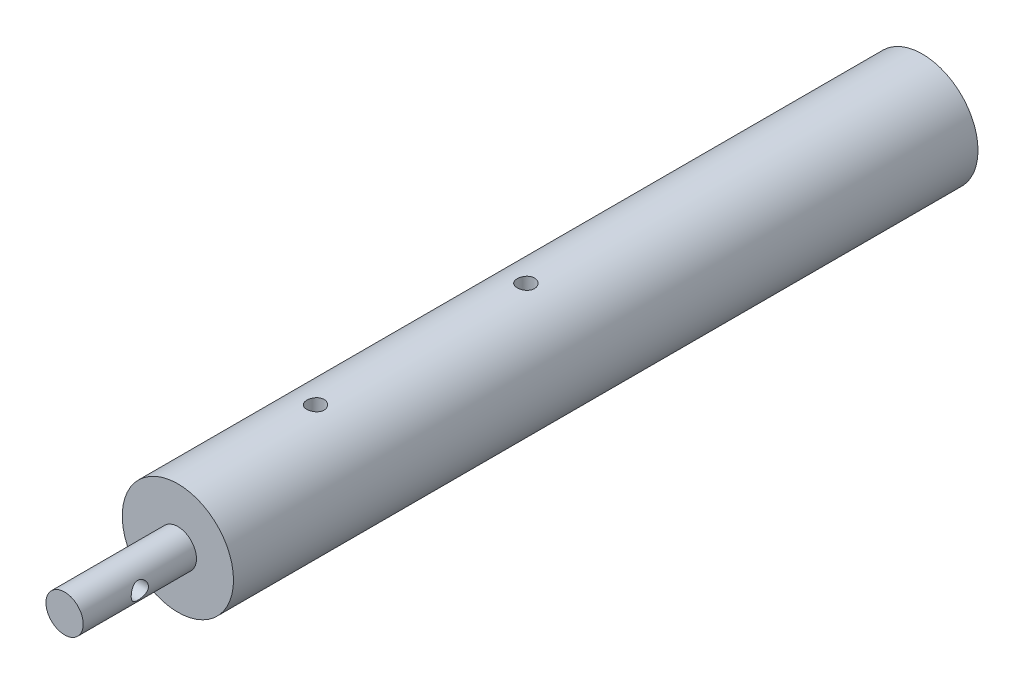
SolidWorks part; units mm, degrees
ref_plane "Front Plane" through (0, 0, 0) normal (0, 0, 1) x (1, 0, 0)
ref_plane "Top Plane" through (0, 0, 0) normal (0, 1, 0) x (1, 0, 0)
ref_plane "Right Plane" through (0, 0, 0) normal (1, 0, 0) x (0, 0, -1)
sketch "Sketch1" plane through (0, 0, 0) normal (0, 0, 1) x (1, 0, 0)
  circle A0 centre (0, 0) radius 8.7312
  dimension "D1" = 17.4625
extrude "Boss-Extrude1" add sketch "Sketch1" along normal blind 116.84
sketch "Sketch2" plane through (0, 0, 116.84) normal (0, 0, 1) x (1, 0, 0)
  circle A0 centre (0, 0) radius 2.921
  dimension "D1" = 5.842
extrude "Boss-Extrude2" add sketch "Sketch2" along normal blind 17.78
ref_plane "Plane1" through (0, 8.7312, 0) normal (0, 1, 0) x (1, 0, 0)
sketch "Sketch4" plane through (0, 8.7312, 0) normal (0, 1, 0) x (1, 0, 0)
  line L1 (-2.921, -134.62) -> (2.921, -134.62) construction
  circle A0 centre (0, -62.23) radius 1.8415
  circle A1 centre (0, -95.25) radius 1.8415
  dimension "D1" = 3.683
  dimension "D2" = 33.02
  dimension "D3" = 39.37
hole_wizard "#6-32 Tapped Hole1" positions "Sketch5" profile "Sketch6" tap size "#6-32" standard "ANSI Inch" end condition through all
sketch "Sketch5" plane through (0, 8.7312, 0) normal (0, 1, 0) x (1, 0, 0)
  point P0 (0, -62.23)
  point P3 (0, -95.25)
sketch "Sketch6" plane through (0, 8.7312, 62.23) normal (1, 0, 0) x (0, 0, 1)
  line L0 (0, 0) -> (0, 17.4625)
  line L1 (0, 17.4625) -> (1.3525, 17.4625)
  line L2 (1.3525, 17.4625) -> (1.3525, 0)
  line L5 (1.3525, 0) -> (0, 0)
  line L11 (0, -6.35) -> (0, 107.95) construction
  dimension "Thru Tap Drill Dia." = 2.7051
  dimension "Thru Tap Drill Depth" = 17.4625
cosmetic thread "Hole Thread1" parameters "D2"=3.5052
cosmetic thread "Hole Thread2" parameters "D2"=3.5052
ref_plane "Plane2" through (2.921, 0, 0) normal (1, 0, 0) x (0, 0, -1)
sketch "Sketch7" plane through (2.921, 0, 0) normal (1, 0, 0) x (0, 0, -1)
  line L1 (-134.62, 2.921) -> (-134.62, -2.921) construction
  circle A0 centre (-125.73, 0) radius 1.8415
  dimension "D1" = 3.683
  dimension "D2" = 8.89
hole_wizard "#6-32 Tapped Hole2" positions "Sketch8" profile "Sketch9" tap size "#6-32" standard "ANSI Inch" end condition through all
sketch "Sketch8" plane through (2.921, 0, 0) normal (1, 0, 0) x (0, 0, -1)
  point P0 (-125.73, 0)
sketch "Sketch9" plane through (2.921, 0, 125.73) normal (0, 1, 0) x (0, 0, -1)
  line L0 (0, 0) -> (0, 11.6522)
  line L1 (0, 11.6522) -> (1.3525, 11.6522)
  line L2 (1.3525, 11.6522) -> (1.3525, 0)
  line L5 (1.3525, 0) -> (0, 0)
  line L11 (0, -6.35) -> (0, 107.95) construction
  dimension "Thru Tap Drill Dia." = 2.7051
  dimension "Thru Tap Drill Depth" = 11.6522
cosmetic thread "Hole Thread3" parameters "D2"=3.5052
